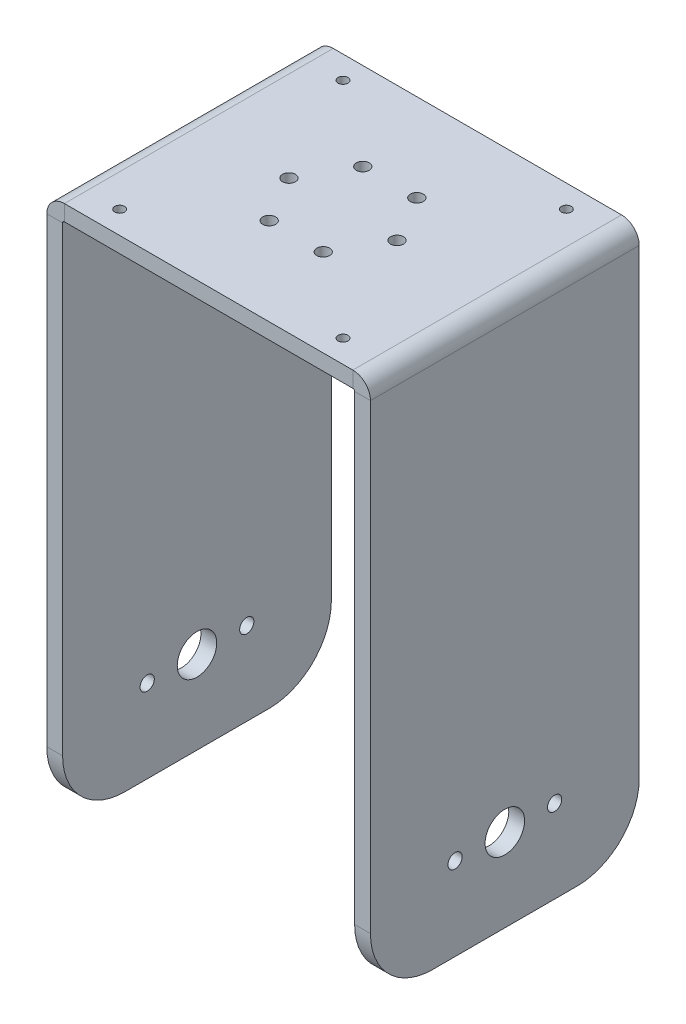
SolidWorks part; units mm, degrees
note: The reader was unsure of these and kept them because the rebuilt part matched: thickness of "Base-Flange1", "Edge-Flange1", "Sheet-Metal2", "Sheet-Metal3", "Sheet-Metal7", "Sheet-Metal10", "Sheet-Metal11"; flange length of "Edge-Flange1".
material "6061-T6 (SS)"
ref_plane "Front Plane" through (0, 0, 0) normal (0, 0, 1) x (1, 0, 0)
ref_plane "Top Plane" through (0, 0, 0) normal (0, 1, 0) x (1, 0, 0)
ref_plane "Right Plane" through (0, 0, 0) normal (1, 0, 0) x (0, 0, -1)
sketch "Sketch3" plane through (0, 0, 0) normal (0, 1, 0) x (1, 0, 0)
  line L1 (-65, 53.975) -> (65, 53.975)
  line L2 (-65, 53.975) -> (-65, -53.975)
  line L3 (-65, -53.975) -> (65, -53.975)
  line L4 (65, 53.975) -> (65, -53.975)
  line L5 (-65, 53.975) -> (65, -53.975) construction
  line L6 (-65, -53.975) -> (65, 53.975) construction
  point P0 (0, 0)
  dimension "D1" = 130
  dimension "D2" = 107.95
base flange "Base-Flange1" sketch "Sketch3" thickness 6.35 reverse thickness direction no parameters "D1"=0.7366
edge flange "Edge-Flange1" sketch "Sketch12" flange angle 90 flange length 217.4875 flange position material inside bend radius 0.7366 thickness 6.35 relief rectangular parameters "D6"=10
sketch "Sketch12" plane through (65, -6.35, 0) normal (-1, 0, 0) x (0, 0, -1)
  line L0 (53.975, 0) -> (-53.975, 0) construction
  line L2 (-53.975, 0) -> (-53.975, 211.1375)
  line L3 (-53.975, 211.1375) -> (53.975, 211.1375)
  line L4 (53.975, 211.1375) -> (53.975, 0)
  line L5 (53.975, 0) -> (-53.975, 0)
  line L6 (-53.975, 177.8) -> (53.975, 177.8) construction
  line L7 (0, 185.7375) -> (-53.975, 185.7375) construction
  line L8 (-20, 177.8) -> (-20, 180.6552) construction
  line L9 (20, 177.8) -> (20, 180.6552) construction
  line L10 (-20, 180.6552) -> (0, 180.6552) construction
  line L11 (0, 180.6552) -> (20, 180.6552) construction
  circle A0 centre (0, 177.8) radius 7.9375
  circle A1 centre (-20, 177.8) radius 2.8552
  circle A2 centre (20, 177.8) radius 2.8552
  dimension "D2" = 177.8
  dimension "D3" = 15.875
  dimension "D1" = 25.4
  dimension "D4" = 2.8552
  dimension "D5" = 20
bend "EdgeBend1" bend radius 0.7366 bend angle 90 parameters "D5"=1
mirror "Mirror1" about plane through (0, 0, 0) normal (1, 0, 0) of "Edge-Flange1"
bend "MirrorBend1" bend radius 0.7366 bend angle 90 parameters "D5"=2
fillet "Fillet1" radius 25 4 edges at (-61.825, -217.4875, 53.975) (-61.825, -217.4875, -53.975) (61.825, -217.4875, -53.975) (61.825, -217.4875, 53.975)
sketch "Sketch13" plane through (0, 0, 0) normal (0, 1, 0) x (1, 0, 0)
  line L0 (-57.9134, 53.975) -> (57.9134, -53.975) construction
  line L1 (57.9134, 53.975) -> (-57.9134, -53.975) construction
  line L2 (-28.4, 0) -> (-15, 0) construction
  circle A0 centre (0, 0) radius 15 construction
  circle A1 centre (0, 0) radius 28.4 construction
  circle A2 centre (-21.7, 0) radius 2.6
  circle A3 centre (-10.85, 18.7928) radius 2.6
  circle A4 centre (10.85, 18.7928) radius 2.6
  circle A5 centre (21.7, 0) radius 2.6
  circle A6 centre (10.85, -18.7928) radius 2.6
  circle A7 centre (-10.85, -18.7928) radius 2.6
  point P28 (0, 0)
  dimension "D1" = 30
  dimension "D2" = 56.8
  dimension "D3" = 5.2
  dimension "D4" = 6
extrude "Flange Coupling Holes" cut sketch "Sketch13" against normal through all normal cut yes
sketch "Sketch15" plane through (0, 0, 0) normal (0, 1, 0) x (1, 0, 0)
  line L1 (-50.8, 50.8) -> (50.8, 50.8) construction
  line L2 (-50.8, 50.8) -> (-50.8, -50.8) construction
  line L3 (-50.8, -50.8) -> (50.8, -50.8) construction
  line L4 (50.8, 50.8) -> (50.8, -50.8) construction
  line L5 (-50.8, 50.8) -> (50.8, -50.8) construction
  line L6 (-50.8, -50.8) -> (50.8, 50.8) construction
  line L7 (-44.845, 44.845) -> (44.845, 44.845) construction
  line L8 (-44.845, 44.845) -> (-44.845, -44.845) construction
  line L9 (-44.845, -44.845) -> (44.845, -44.845) construction
  line L10 (44.845, 44.845) -> (44.845, -44.845) construction
  line L11 (-44.845, 44.845) -> (44.845, -44.845) construction
  circle A0 centre (-44.845, 44.845) radius 1.985
  circle A1 centre (44.845, 44.845) radius 1.985
  circle A2 centre (44.845, -44.845) radius 1.985
  circle A3 centre (-44.845, -44.845) radius 1.985
  point P4 (0, 0)
  point P12 (1.0695, -1.0695)
  point P21 (0, 0)
  dimension "D3" = 3.97
  dimension "D4" = 4
  dimension "D1" = 101.6
  dimension "D2" = 89.69
extrude "Cut-Extrude1" cut sketch "Sketch15" against normal through all normal cut yes
sketch "Bend-Lines1" [suppressed] plane through (0, 0, 0) normal (0, 1, 0) x (1, 0, 0)
sketch "Bounding-Box1" [suppressed] plane through (0, 0, 0) normal (0, 1, 0) x (1, 0, 0)
sheet metal parameters "Sheet-Metal2" thickness 6.35 parameters "D1"=0.7366, "D7"=0.7366
flat pattern "Flat-Pattern2" [suppressed]
sketch "Bend-Lines2" plane through (0, 0, 0) normal (0, 1, 0) x (1, 0, 0)
sketch3d "Bounding-Box2" [suppressed]
  line L0 (-70, 35, 0) -> (70, 35, 0) construction
  line L1 (-70, -35, 0) -> (70, -35, 0) construction
  line L2 (-70, 35, 0) -> (-70, -35, 0) construction
  line L3 (70, 35, 0) -> (70, -35, 0) construction
sheet metal parameters "Sheet-Metal3" thickness 6.35 parameters "D1"=0.7366, "D7"=0.7366
flat pattern "Flat-Pattern2"
sketch "Bend-Lines2" plane through (0, 0, 0) normal (0, 1, 0) x (1, 0, 0)
  line L0 (40.9856, -42.5) -> (40.9856, 42.5) construction
  line L1 (40.9856, -42.5) -> (40.9856, 42.5) construction
sketch3d "Bounding-Box2" [suppressed]
  line L0 (243.3211, 42.5, 0) -> (-45, 42.5, 0) construction
  line L1 (243.3211, -42.5, 0) -> (-45, -42.5, 0) construction
  line L2 (243.3211, 42.5, 0) -> (243.3211, -42.5, 0) construction
  line L3 (-45, 42.5, 0) -> (-45, -42.5, 0) construction
bend of the flat pattern "Flatten-<EdgeBend1>1"
sheet metal parameters "Sheet-Metal7" thickness 6.35 parameters "D1"=0.7366, "D7"=0.7366
flat pattern "Flat-Pattern2"
sketch "Bend-Lines2" plane through (0, 0, 0) normal (0, 1, 0) x (1, 0, 0)
  line L0 (60.9856, -47.5) -> (60.9856, 47.5) construction
  line L1 (60.9856, -47.5) -> (60.9856, 47.5) construction
  line L2 (-60.9856, 47.5) -> (-60.9856, -47.5) construction
  line L3 (-60.9856, 47.5) -> (-60.9856, -47.5) construction
sketch3d "Bounding-Box2" [suppressed]
  line L0 (-274.4586, 47.5, 0) -> (274.4586, 47.5, 0) construction
  line L1 (-274.4586, -47.5, 0) -> (274.4586, -47.5, 0) construction
  line L2 (-274.4586, 47.5, 0) -> (-274.4586, -47.5, 0) construction
  line L3 (274.4586, 47.5, 0) -> (274.4586, -47.5, 0) construction
bend of the flat pattern "Flatten-<EdgeBend1>1"
bend of the flat pattern "Flatten-<MirrorBend1>1"
sheet metal parameters "Sheet-Metal10" thickness 6.35 parameters "D1"=0.7366, "D7"=0.7366
flat pattern "Flat-Pattern2"
sketch "Bend-Lines2" plane through (0, 0, 0) normal (0, 1, 0) x (1, 0, 0)
  line L0 (60.9856, -47.5) -> (60.9856, 47.5) construction
  line L1 (60.9856, -47.5) -> (60.9856, 47.5) construction
  line L2 (-60.9856, 47.5) -> (-60.9856, -47.5) construction
  line L3 (-60.9856, 47.5) -> (-60.9856, -47.5) construction
sketch3d "Bounding-Box2" [suppressed]
  line L0 (-274.4586, 47.5, 0) -> (274.4586, 47.5, 0) construction
  line L1 (-274.4586, -47.5, 0) -> (274.4586, -47.5, 0) construction
  line L2 (-274.4586, 47.5, 0) -> (-274.4586, -47.5, 0) construction
  line L3 (274.4586, 47.5, 0) -> (274.4586, -47.5, 0) construction
bend of the flat pattern "Flatten-<EdgeBend1>1"
bend of the flat pattern "Flatten-<MirrorBend1>1"
sheet metal parameters "Sheet-Metal11" thickness 6.35 parameters "D1"=0.7366, "D7"=0.7366
flat pattern "Flat-Pattern2"
sketch "Bend-Lines2" plane through (0, 0, 0) normal (0, 1, 0) x (1, 0, 0)
  line L0 (60.9856, -53.975) -> (60.9856, 53.975) construction
  line L1 (60.9856, -53.975) -> (60.9856, 53.975) construction
  line L2 (-60.9856, 53.975) -> (-60.9856, -53.975) construction
  line L3 (-60.9856, 53.975) -> (-60.9856, -53.975) construction
sketch3d "Bounding-Box2" [suppressed]
  line L0 (-274.4586, 53.975, 0) -> (274.4586, 53.975, 0) construction
  line L1 (-274.4586, -53.975, 0) -> (274.4586, -53.975, 0) construction
  line L2 (-274.4586, 53.975, 0) -> (-274.4586, -53.975, 0) construction
  line L3 (274.4586, 53.975, 0) -> (274.4586, -53.975, 0) construction
bend of the flat pattern "Flatten-<EdgeBend1>1"
bend of the flat pattern "Flatten-<MirrorBend1>1"
